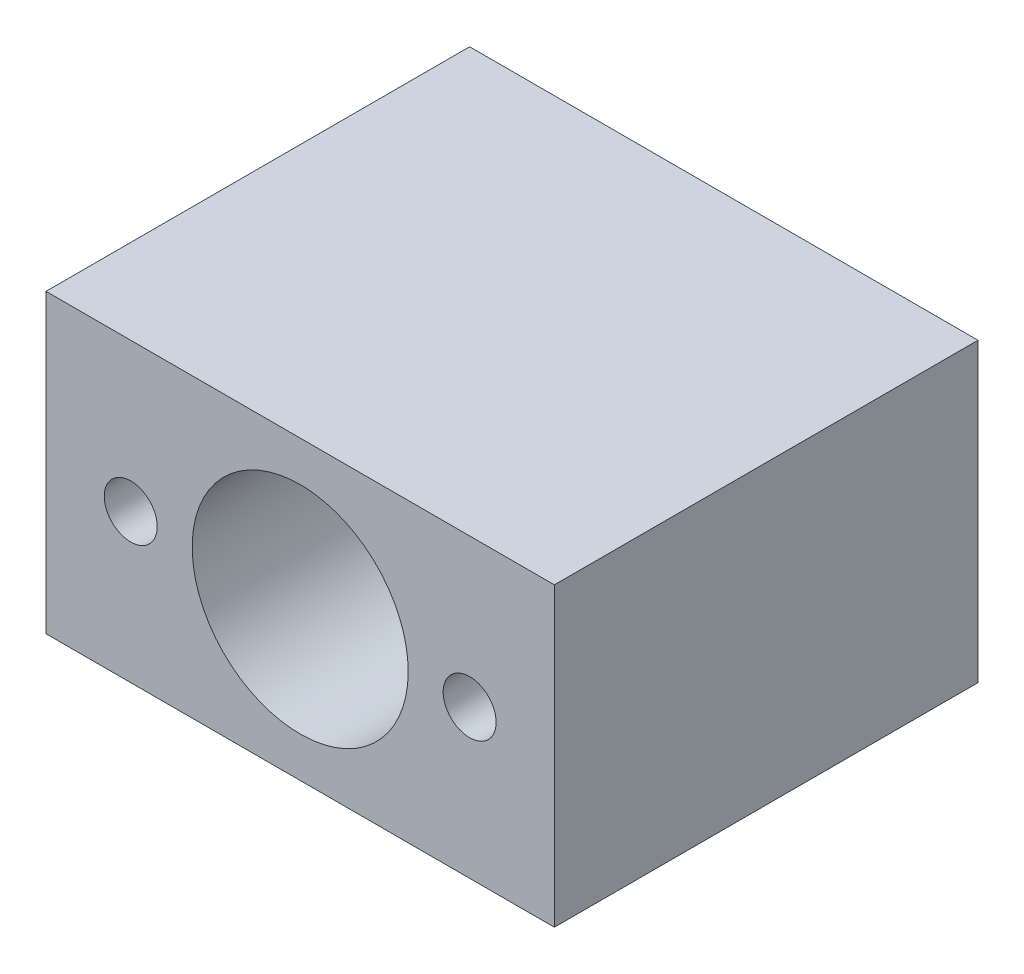
SolidWorks part; units mm, degrees
ref_plane "Alzado" through (0, 0, 0) normal (0, 0, 1) x (1, 0, 0)
ref_plane "Planta" through (0, 0, 0) normal (0, 1, 0) x (1, 0, 0)
ref_plane "Vista lateral" through (0, 0, 0) normal (1, 0, 0) x (0, 0, -1)
sketch "Croquis1" plane through (0, 0, 0) normal (0, 0, 1) x (1, 0, 0)
  line L1 (0, 0) -> (24, 0)
  line L2 (0, 0) -> (0, 14)
  line L3 (0, 14) -> (24, 14)
  line L4 (24, 0) -> (24, 14)
  circle A0 centre (12, 7) radius 5.1
  circle A1 centre (4, 7) radius 1.25
  circle A2 centre (20, 7) radius 1.25
  dimension "D5" = 2.5
  dimension "D6" = 2.5
  dimension "D9" = 10.2
  dimension "D1" = 14
  dimension "D2" = 24
  dimension "D3" = 12
  dimension "D4" = 7
  dimension "D7" = 8
  dimension "D8" = 8
extrude "Saliente-Extruir1" add sketch "Croquis1" along normal blind 20
